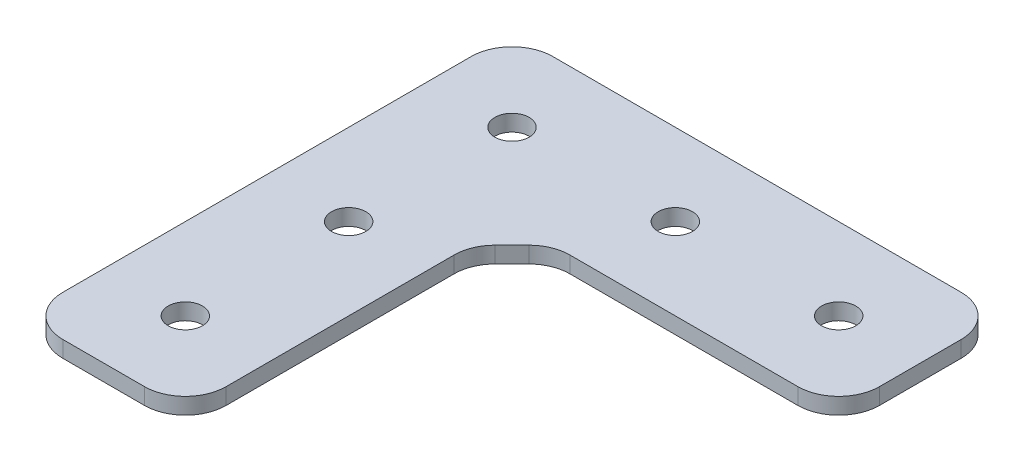
SolidWorks part; units mm, degrees
ref_plane "Front Plane" through (0, 0, 0) normal (0, 0, 1) x (1, 0, 0)
ref_plane "Top Plane" through (0, 0, 0) normal (0, 1, 0) x (1, 0, 0)
ref_plane "Right Plane" through (0, 0, 0) normal (1, 0, 0) x (0, 0, -1)
sketch "Sketch1" plane through (0, 0, 0) normal (0, 1, 0) x (1, 0, 0)
  line L0 (-10, 10) -> (50, 10)
  line L2 (-10, 10) -> (-10, -50)
  line L3 (-10, -50) -> (10, -50)
  line L4 (10, -10) -> (10, -50)
  line L5 (-10, 10) -> (10, -50) construction
  line L7 (50, 10) -> (50, -10)
  line L8 (50, -10) -> (10, -10)
  circle A0 centre (0, 0) radius 2.1
  circle A1 centre (20, 0) radius 2.1
  circle A2 centre (40, 0) radius 2.1
  circle A3 centre (0, -20) radius 2.1
  circle A4 centre (0, -40) radius 2.1
  dimension "D1" = 4.2
  dimension "D3" = 20
  dimension "D5" = 20
  dimension "D8" = 20
  dimension "D6" = 20
  dimension "D7" = 60
  dimension "D9" = 60
  dimension "D10" = 10
  dimension "D2" = 3
  dimension "D4" = 3
base flange "Base-Flange1" sketch "Sketch1" thickness 2 reverse thickness direction no parameters "D1"=3
chamfer "Chamfer1" [suppressed] distance 40 angle 45
fillet "Fillet_Shape" radius 5 5 edges at (-10, -1, 50) (10, -1, 50) (50, -1, 10) (50, -1, -10) (-10, -1, -10)
fillet "Fillet1" [suppressed] radius 5
chamfer "Chamfer2" distance 5 angle 45 1 edges at (10, -1, 10)
fillet "Fillet2" radius 5 2 edges at (10, -1, 15) (15, -1, 10)
sketch "Bend-Lines1" [suppressed] plane through (0, 0, 0) normal (0, 1, 0) x (1, 0, 0)
sketch "Bounding-Box1" [suppressed] plane through (0, 0, 0) normal (0, 1, 0) x (1, 0, 0)
sheet metal parameters "Sheet-Metal2" thickness 2 parameters "D1"=3
flat pattern "Flat-Pattern2" [suppressed]
sketch "Bend-Lines2" plane through (0, 0, 0) normal (0, 1, 0) x (1, 0, 0)
sketch3d "Bounding-Box2" [suppressed]
  line L0 (50, 10, 0) -> (50, -50, 0) construction
  line L1 (-10, 10, 0) -> (-10, -50, 0) construction
  line L2 (50, 10, 0) -> (-10, 10, 0) construction
  line L3 (50, -50, 0) -> (-10, -50, 0) construction
